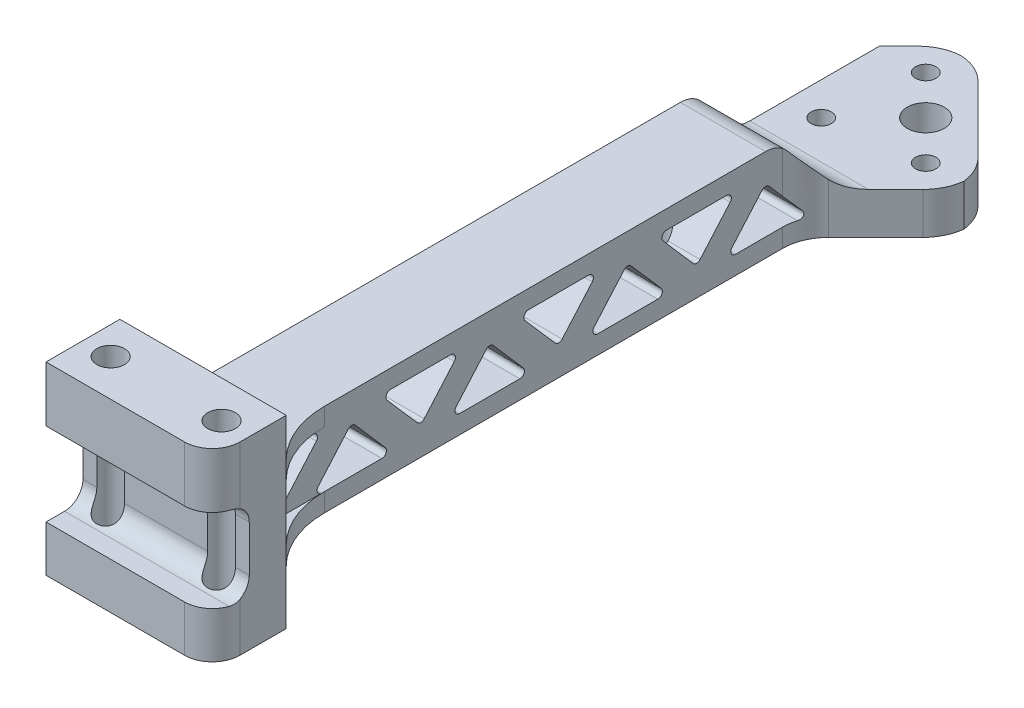
SolidWorks part; units mm, degrees
ref_plane "Front Plane" through (0, 0, 0) normal (0, 0, 1) x (1, 0, 0)
ref_plane "Top Plane" through (0, 0, 0) normal (0, 1, 0) x (1, 0, 0)
ref_plane "Right Plane" through (0, 0, 0) normal (1, 0, 0) x (0, 0, -1)
sketch "Sketch1" plane through (0, 0, 0) normal (0, 1, 0) x (1, 0, 0)
  line L0 (0, 90.2116) -> (0, 0)
  line L1 (0, 0) -> (15, 0)
  line L2 (18, 3) -> (18, 8)
  line L3 (18, 8) -> (12.1524, 13.8476)
  line L4 (9.2234, 20.9187) -> (9.2234, 72.565)
  line L5 (3, 4) -> (15, 4) construction
  line L6 (9.2234, 72.565) -> (9.2234, 86) construction
  line L7 (0, 90.2116) -> (3.5311, 93.7426)
  line L8 (3.5311, 93.7426) -> (7.1377, 93.7426)
  line L9 (7.1377, 93.7426) -> (17.2694, 83.6109)
  line L10 (17.2694, 83.6109) -> (17.2694, 80.6109)
  line L11 (17.2694, 80.6109) -> (9.2234, 72.565)
  line L12 (9.2234, 86) -> (13.4661, 81.7574) construction
  line L13 (4.9808, 90.2426) -> (9.2234, 86) construction
  line L14 (9.2234, 86) -> (3.5666, 80.3431) construction
  circle A0 centre (9.2234, 86) radius 6 construction
  circle A1 centre (9.2234, 86) radius 8 construction
  circle A2 centre (3, 4) radius 1.5
  circle A3 centre (15, 4) radius 1.5
  arc A4 (18, 3) -> (15, 0) centre (15, 3) cw
  circle A5 centre (13.4661, 81.7574) radius 1.1
  circle A6 centre (3.5666, 80.3431) radius 1.1
  circle A7 centre (4.9808, 90.2426) radius 1.1
  circle A8 centre (9.2234, 86) radius 2
  arc A9 (12.1524, 13.8476) -> (9.2234, 20.9187) centre (19.2234, 20.9187) cw
  point P15 (18, 0)
  point P28 (0, 0)
  point P29 (17.7217, 83.1586)
  dimension "D8" = 3
  dimension "D9" = 3
  dimension "D7" = 16
  dimension "D11" = 12
  dimension "D16" = 2.2
  dimension "D17" = 4
  dimension "D23" = 10
  dimension "D1" = 18
  dimension "D2" = 8
  dimension "D3" = 12
  dimension "D4" = 3
  dimension "D5" = 4
  dimension "D6" = 45
  dimension "D10" = 82
  dimension "D12" = 45
  dimension "D13" = 90
  dimension "D14" = 90
  dimension "D15" = 3.5
  dimension "D18" = 3.5
  dimension "D19" = 45
  dimension "D20" = 3.5
  dimension "D21" = 4
  dimension "D22" = 3
extrude "Boss-Extrude1" add sketch "Sketch1" along normal blind 10
sketch "Sketch2" plane through (0, 0, 0) normal (-1, 0, 0) x (0, 0, 1)
  line L0 (-93.7426, 8) -> (1.749, 8) construction
  line L1 (-93.7426, 10) -> (-93.7426, 0) construction
  line L2 (1.749, 8) -> (1.749, 7) construction
  line L3 (1.749, 7) -> (-93.7426, 7) construction
  line L4 (-93.7426, 7) -> (-93.7426, 5) construction
  line L5 (-93.7426, 5) -> (1.749, 5) construction
  line L6 (1.749, 5) -> (1.749, 3) construction
  line L7 (1.749, 3) -> (-95.5541, 3) construction
  line L8 (-95.5541, 3) -> (-95.5541, 2) construction
  line L9 (-95.5541, 2) -> (-93.5541, 2) construction
  line L10 (-90.2116, 10) -> (0, 10) construction
  line L11 (-8, 8.0818) -> (-8, 2)
  line L12 (-8, 2) -> (-13.3, 2)
  line L13 (-93.7426, 0) -> (-90.2116, 0) construction
  line L14 (-13.3, 2) -> (-8, 8.0818)
  line L15 (-12.0506, 8) -> (-16.4078, 3)
  line L16 (-16.4078, 3) -> (-20.7651, 8)
  line L17 (-20.7651, 8) -> (-12.0506, 8)
  line L18 (-23.8729, 7) -> (-19.5157, 2)
  line L19 (-19.5157, 2) -> (-28.2302, 2)
  line L20 (-28.2302, 2) -> (-23.8729, 7)
  line L21 (-26.9808, 8) -> (-31.338, 3)
  line L22 (-31.338, 3) -> (-35.6953, 8)
  line L23 (-35.6953, 8) -> (-26.9808, 8)
  line L24 (-41.911, 8) -> (-46.2682, 3)
  line L25 (-46.2682, 3) -> (-50.6254, 8)
  line L26 (-50.6254, 8) -> (-41.911, 8)
  line L27 (-56.8411, 8) -> (-61.1984, 3)
  line L28 (-61.1984, 3) -> (-65.5556, 8)
  line L29 (-65.5556, 8) -> (-56.8411, 8)
  line L30 (-38.8031, 7) -> (-34.4459, 2)
  line L31 (-43.1604, 2) -> (-38.8031, 7)
  line L32 (-34.4459, 2) -> (-43.1604, 2)
  line L33 (-53.7333, 7) -> (-49.376, 2)
  line L34 (-58.0905, 2) -> (-53.7333, 7)
  line L35 (-49.376, 2) -> (-58.0905, 2)
  line L36 (-68.6635, 7) -> (-64.3062, 2)
  line L37 (-73.0207, 2) -> (-68.6635, 7)
  line L38 (-64.3062, 2) -> (-73.0207, 2)
  line L39 (-77, 8) -> (-77, 2)
  line L40 (-77, 2) -> (-71.7713, 8)
  line L41 (-71.7713, 8) -> (-77, 8)
  line L42 (0, 10) -> (0, 0) construction
  point P49 (0, 0)
  point P50 (0, 0)
  point P51 (0, 0)
  point P52 (0, 0)
  point P53 (-73.9334, 2)
  point P54 (-96.4393, 2.119)
  point P55 (-99.3077, 11.2096)
  dimension "D1" = 2
  dimension "D2" = 2
  dimension "D3" = 1
  dimension "D4" = 1
  dimension "D5" = 5.3
  dimension "D6" = 3
  dimension "D7" = 3
  dimension "D10" = 8
  dimension "D11" = 77
  dimension "D12" = 3
  dimension "D13" = 3
  dimension "D14" = 3
  dimension "D8" = 4
  dimension "D9" = 4
extrude "Cut-Extrude1" cut sketch "Sketch2" against normal up to next
sketch "Sketch3" plane through (9.2234, 0, 0) normal (1, 0, 0) x (0, 0, -1)
  line L1 (8, 8.0818) -> (20.9187, 8.0818)
  line L2 (8, 8.0818) -> (8, 2)
  line L3 (8, 2) -> (20.9187, 2)
  line L4 (20.9187, 8.0818) -> (20.9187, 2)
extrude "Cut-Extrude2" cut sketch "Sketch3" along normal blind 30
fillet "Fillet70" radius 0.5 29 edges at (4.6117, 3, -61.1984) (4.6117, 3, -46.2682) (4.6117, 3, -31.338) (4.6117, 8, -26.9808) (4.6117, 8, -41.911) (4.6117, 8, -56.8411) (4.6117, 8, -71.7713) (6.8292, 2, -77) (4.6117, 2, -64.3062) (4.6117, 2, -49.376) (4.6117, 2, -34.4459) (4.6117, 2, -19.5157) (4.6117, 2, -28.2302) (4.6117, 2, -43.1604) (4.6117, 2, -58.0905) (4.8396, 2, -73.0207) (4.6117, 8, -65.5556) (4.6117, 8, -50.6254) (4.6117, 8, -35.6953) (6.8292, 8, -77) (4.6117, 7, -68.6635) (4.6117, 7, -53.7333) (4.6117, 7, -38.8031) (4.6117, 7, -23.8729) (4.6117, 3, -16.4078) (4.6117, 2, -13.3) (4.6117, 8, -20.7651) (9, 2, -8) (4.6117, 8, -12.0506)
sketch "Sketch4" plane through (0, 10, 0) normal (0, 1, 0) x (1, 0, 0)
  line L0 (18, 8) -> (0, 8)
  line L1 (0, 90.2116) -> (0, 0) construction
  line L2 (0, 8) -> (0, 0)
  line L3 (0, 0) -> (15, 0)
  line L4 (18, 3) -> (18, 8) construction
  line L5 (18, 3) -> (18, 8)
  arc A0 (15, 0) -> (18, 3) centre (15, 3) ccw construction
  arc A1 (15, 0) -> (18, 3) centre (15, 3) ccw
  circle A2 centre (3, 4) radius 1.5 construction
  circle A3 centre (15, 4) radius 1.5 construction
  circle A4 centre (3, 4) radius 1.5
  circle A5 centre (15, 4) radius 1.5
extrude "Boss-Extrude2" add sketch "Sketch4" along normal blind 10
sketch "Sketch6" plane through (0, 0, 0) normal (-1, 0, 0) x (0, 0, 1)
  line L0 (0, 20) -> (0, 0) construction
  line L1 (0, 14) -> (-4, 14)
  line L2 (0, 14) -> (0, 5)
  line L3 (0, 5) -> (-4, 5)
  line L4 (-4, 14) -> (-4, 5)
  line L5 (-90.2116, 0) -> (0, 0) construction
  line L6 (-8, 20) -> (0, 20) construction
  dimension "D1" = 5
  dimension "D2" = 6
  dimension "D3" = 4
extrude "Cut-Extrude3" cut sketch "Sketch6" against normal through all
sketch "Sketch7" plane through (0, 0, 0) normal (-1, 0, 0) x (0, 0, 1)
  line L0 (-8, 20) -> (-8, 10)
  line L1 (-8, 10) -> (-18, 10)
  line L2 (-90.2116, 10) -> (-8, 10) construction
  line L3 (-18, 10) -> (-8, 20)
  dimension "D1" = 45
extrude "Boss-Extrude3" add sketch "Sketch7" against normal blind 10
sketch "Sketch8" plane through (0, 0, 0) normal (-1, 0, 0) x (0, 0, 1)
  line L3 (-77, 7.5) -> (-77, 3.3348)
  line L4 (-72.8703, 8) -> (-76.5, 8)
  line L5 (-76.123, 3.0063) -> (-72.4933, 7.1715)
  line L6 (-77, 7.5) -> (-77, 3.3348)
  line L7 (-72.8703, 8) -> (-76.5, 8)
  line L8 (-76.123, 3.0063) -> (-72.4933, 7.1715)
  arc A3 (-76.5, 8) -> (-77, 7.5) centre (-76.5, 7.5) ccw
  arc A4 (-72.4933, 7.1715) -> (-72.8703, 8) centre (-72.8703, 7.5) ccw
  arc A5 (-77, 3.3348) -> (-76.123, 3.0063) centre (-76.5, 3.3348) ccw
  arc A6 (-76.5, 8) -> (-77, 7.5) centre (-76.5, 7.5) ccw
  arc A7 (-72.4933, 7.1715) -> (-72.8703, 8) centre (-72.8703, 7.5) ccw
  arc A8 (-77, 3.3348) -> (-76.123, 3.0063) centre (-76.5, 3.3348) ccw
  dimension "D1" = 0
extrude "Boss-Extrude4" add sketch "Sketch8" against normal up to surface (13.6585 mm away) up to face at (12.2206, 5.8774, -75.5622)
sketch "Sketch9" plane through (0, 0, 0) normal (-1, 0, 0) x (0, 0, 1)
  line L0 (-70.0284, 10) -> (-74.8214, 4.5)
  line L1 (-90.2116, 10) -> (-18, 10) construction
  line L2 (-74.8214, 4.5) -> (-98.7773, 4.5)
  line L3 (-98.7773, 4.5) -> (-98.7773, 10)
  line L4 (-98.7773, 10) -> (-70.0284, 10)
  line L5 (-69.0404, 6.5674) -> (-72.2987, 2.8285) construction
  line L6 (-90.2116, 0) -> (0, 0) construction
  dimension "D1" = 3
  dimension "D2" = 4.5
extrude "Cut-Extrude4" cut sketch "Sketch9" against normal through all
fillet "Fillet71" radius 2 2 edges at (9, 5, -4) (9, 14, -4)
chamfer "Chamfer1" distance 7 angle 50 1 edges at (10, 15, -13) first distance on face at (10, 12.5, -12.7637)
fillet "Fillet72" radius 2 3 edges at (14, 10, -8) (5.8289, 10, -13.0503) (5.8289, 15.0503, -8)
fillet "Fillet73" radius 3 2 edges at (5.7399, 4.5, -74.8214) (4.6117, 10, -70.0284)
fillet "Fillet74" radius 5 5 edges at (9.2234, 3.5446, -72.565) (17.2694, 2.25, -83.6109) (17.2694, 2.25, -80.6109) (7.1377, 2.25, -93.7426) (3.5311, 2.25, -93.7426)
sketch "Sketch10" plane through (0, 0, 0) normal (0, -1, 0) x (1, 0, 0)
  line L0 (0, -90.2116) -> (0, 0) construction
  circle A0 centre (4.5, -61.5855) radius 1.25
  dimension "D1" = 2.5
  dimension "D2" = 4.5
  dimension "D3" = 32.15
extrude "Cut-Extrude5" cut sketch "Sketch10" against normal blind 6
